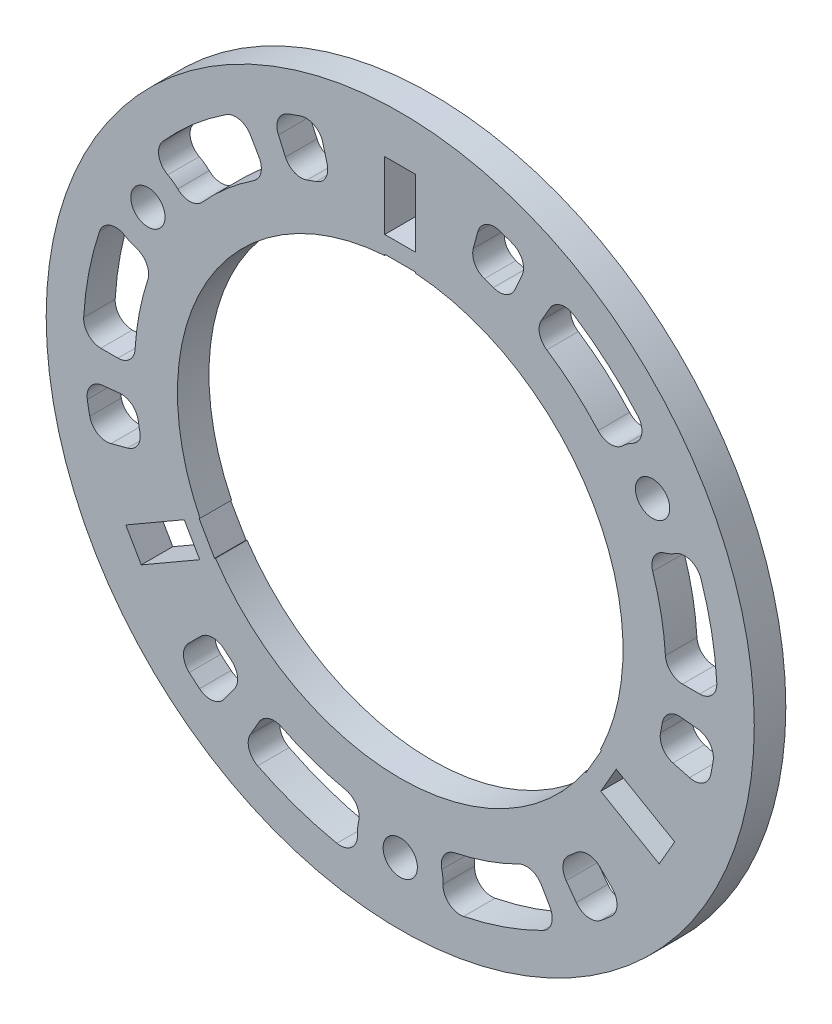
SolidWorks part; units mm, degrees
ref_plane "Front Plane" through (0, 0, 0) normal (0, 0, 1) x (1, 0, 0)
ref_plane "Top Plane" through (0, 0, 0) normal (0, 1, 0) x (1, 0, 0)
ref_plane "Right Plane" through (0, 0, 0) normal (1, 0, 0) x (0, 0, -1)
sketch "Sketch1" plane through (0, 0, 0) normal (0, 0, 1) x (1, 0, 0)
  line L0 (0, 0) -> (0, 50.8) construction
  line L1 (47.9712, -31.0114) -> (50.8422, -26.0386)
  line L2 (2.871, 57.05) -> (-2.871, 57.05)
  line L3 (2.871, 57.05) -> (2.871, 44.55)
  line L4 (2.871, 44.55) -> (-2.871, 44.55)
  line L5 (-2.871, 57.05) -> (-2.871, 44.55)
  line L6 (2.871, 57.05) -> (-2.871, 44.55) construction
  line L7 (2.871, 44.55) -> (-2.871, 57.05) construction
  line L8 (47.9712, -31.0114) -> (37.1459, -24.7614)
  line L9 (37.1459, -24.7614) -> (40.0169, -19.7886)
  line L10 (50.8422, -26.0386) -> (40.0169, -19.7886)
  line L11 (47.9712, -31.0114) -> (40.0169, -19.7886) construction
  line L12 (37.1459, -24.7614) -> (50.8422, -26.0386) construction
  line L13 (-50.8422, -26.0386) -> (-47.9712, -31.0114)
  line L14 (-50.8422, -26.0386) -> (-40.0169, -19.7886)
  line L15 (-40.0169, -19.7886) -> (-37.1459, -24.7614)
  line L16 (-47.9712, -31.0114) -> (-37.1459, -24.7614)
  line L17 (-50.8422, -26.0386) -> (-37.1459, -24.7614) construction
  line L18 (-40.0169, -19.7886) -> (-47.9712, -31.0114) construction
  line L19 (-2.871, 41.375) -> (2.871, 41.375)
  line L20 (-2.871, 41.175) -> (-2.871, 41.375)
  line L21 (2.871, 41.175) -> (2.871, 41.375)
  line L22 (34.2231, -23.0739) -> (34.3963, -23.1739)
  line L23 (37.2673, -18.2011) -> (34.3963, -23.1739)
  line L24 (37.0941, -18.1012) -> (37.2673, -18.2011)
  line L25 (-37.0941, -18.1012) -> (-37.2673, -18.2011)
  line L26 (-34.3963, -23.1739) -> (-37.2673, -18.2011)
  line L27 (0, 0) -> (32.5438, 56.3674) construction
  line L28 (-34.2231, -23.0739) -> (-34.3963, -23.1739)
  arc A0 (-2.871, 41.175) -> (-37.0941, -18.1012) centre (0, 0) ccw
  circle A1 centre (0, 0) radius 65.0875
  circle A2 centre (0, 0) radius 50.8 construction
  arc A3 (37.0941, -18.1012) -> (2.871, 41.175) centre (0, 0) ccw
  arc A4 (-34.2231, -23.0739) -> (34.2231, -23.0739) centre (0, 0) ccw
  point P21 (0, 0)
  point P32 (0, 0)
  point P34 (0, 0)
  dimension "D1" = 82.55
  dimension "D2" = 130.175
  dimension "D8" = 3.175
  dimension "D10" = 101.6
  dimension "D3" = 50.8
  dimension "D4" = 12.5
  dimension "D5" = 5.742
  dimension "D7" = 30
  dimension "D6" = 3
  dimension "D9" = 3
extrude "Boss-Extrude1" add sketch "Sketch1" along normal blind 5.842
sketch "Sketch3" plane through (0, 0, 5.842) normal (0, 0, 1) x (1, 0, 0)
  line L0 (0, 0) -> (0, 65.0875) construction
  line L1 (0, 0) -> (-56.3674, 32.5437) construction
  line L2 (-24.6063, 42.6193) -> (-29.3688, 50.8682)
  line L3 (-49.2125, 0) -> (-58.7375, 0)
  line L4 (-41.2731, 26.803) -> (-49.2614, 31.9907)
  line L5 (-43.8487, 22.342) -> (-52.3355, 26.6663)
  line L6 (43.8487, 22.342) -> (52.3355, 26.6663)
  line L7 (41.2731, 26.803) -> (49.2614, 31.9907)
  line L8 (24.6063, 42.6193) -> (29.3688, 50.8682)
  line L9 (49.2125, 0) -> (58.7375, 0)
  line L10 (-2.5756, -49.1451) -> (-3.0741, -58.657)
  line L11 (2.5756, -49.1451) -> (3.0741, -58.657)
  line L12 (24.6062, -42.6193) -> (29.3687, -50.8682)
  line L13 (-24.6063, -42.6193) -> (-29.3688, -50.8682)
  line L14 (-20.0165, 44.9579) -> (-23.8907, 53.6594)
  line L15 (-15.2024, 56.7361) -> (-12.7371, 47.5356)
  line L16 (-56.7361, -15.2024) -> (-47.5356, -12.7371)
  line L17 (-48.9429, -5.1441) -> (-58.4157, -6.1397)
  line L18 (48.9429, -5.1441) -> (58.4157, -6.1397)
  line L19 (56.7361, -15.2024) -> (47.5356, -12.7371)
  line L20 (15.2024, 56.7361) -> (12.7371, 47.5356)
  line L21 (20.0165, 44.9579) -> (23.8907, 53.6594)
  line L22 (-28.9264, -39.8137) -> (-34.525, -47.5196)
  line L23 (-41.5337, -41.5337) -> (-34.7985, -34.7985)
  line L24 (41.5337, -41.5337) -> (34.7985, -34.7985)
  line L25 (28.9264, -39.8137) -> (34.525, -47.5196)
  circle A0 centre (0, 0) radius 65.0875 construction
  arc A1 (-29.3688, 50.8682) -> (-49.2614, 31.9907) centre (0, 0) ccw
  arc A2 (-24.6063, 42.6193) -> (-41.2731, 26.803) centre (0, 0) ccw
  arc A3 (-43.8487, 22.342) -> (-49.2125, 0) centre (0, 0) ccw
  circle A4 centre (0, 0) radius 49.2125 construction
  circle A5 centre (0, 0) radius 58.7375 construction
  arc A6 (-52.3355, 26.6663) -> (-58.7375, 0) centre (0, 0) ccw
  arc A7 (58.7375, 0) -> (52.3355, 26.6663) centre (0, 0) ccw
  arc A8 (49.2614, 31.9907) -> (29.3688, 50.8682) centre (0, 0) ccw
  arc A9 (41.2731, 26.803) -> (24.6063, 42.6193) centre (0, 0) ccw
  arc A10 (49.2125, 0) -> (43.8487, 22.342) centre (0, 0) ccw
  arc A11 (-29.3688, -50.8682) -> (-3.0741, -58.657) centre (0, 0) ccw
  arc A12 (3.0741, -58.657) -> (29.3687, -50.8682) centre (0, 0) ccw
  arc A13 (2.5756, -49.1451) -> (24.6062, -42.6193) centre (0, 0) ccw
  arc A14 (-24.6063, -42.6193) -> (-2.5756, -49.1451) centre (0, 0) ccw
  arc A15 (-24.6063, 42.6193) -> (-41.2731, 26.803) centre (0, 0) ccw
  arc A16 (-29.3688, 50.8682) -> (-49.2614, 31.9907) centre (0, 0) ccw
  arc A17 (-43.8487, 22.342) -> (-49.2125, 0) centre (0, 0) ccw
  arc A18 (-52.3355, 26.6663) -> (-58.7375, 0) centre (0, 0) ccw
  arc A19 (-24.6063, -42.6193) -> (-2.5756, -49.1451) centre (0, 0) ccw
  arc A20 (-29.3688, -50.8682) -> (-3.0741, -58.657) centre (0, 0) ccw
  arc A21 (2.5756, -49.1451) -> (24.6062, -42.6193) centre (0, 0) ccw
  arc A22 (3.0741, -58.657) -> (29.3687, -50.8682) centre (0, 0) ccw
  arc A23 (58.7375, 0) -> (52.3355, 26.6663) centre (0, 0) ccw
  arc A24 (49.2125, 0) -> (43.8487, 22.342) centre (0, 0) ccw
  arc A25 (41.2731, 26.803) -> (24.6063, 42.6193) centre (0, 0) ccw
  arc A26 (49.2614, 31.9907) -> (29.3688, 50.8682) centre (0, 0) ccw
  arc A27 (-12.7371, 47.5356) -> (-20.0165, 44.9579) centre (0, 0) ccw
  arc A28 (-15.2024, 56.7361) -> (-23.8907, 53.6594) centre (0, 0) ccw
  arc A29 (-56.7361, -15.2024) -> (-58.4157, -6.1397) centre (0, 0) cw
  arc A30 (-47.5356, -12.7371) -> (-48.9429, -5.1441) centre (0, 0) cw
  arc A31 (56.7361, -15.2024) -> (58.4157, -6.1397) centre (0, 0) ccw
  arc A32 (47.5356, -12.7371) -> (48.9429, -5.1441) centre (0, 0) ccw
  arc A33 (15.2024, 56.7361) -> (23.8907, 53.6594) centre (0, 0) cw
  arc A34 (12.7371, 47.5356) -> (20.0165, 44.9579) centre (0, 0) cw
  arc A35 (-41.5337, -41.5337) -> (-34.525, -47.5196) centre (0, 0) ccw
  arc A36 (-34.7985, -34.7985) -> (-28.9264, -39.8137) centre (0, 0) ccw
  arc A37 (41.5337, -41.5337) -> (34.525, -47.5196) centre (0, 0) cw
  arc A38 (34.7985, -34.7985) -> (28.9264, -39.8137) centre (0, 0) cw
  point P8 (56.171, 17.1732)
  point P13 (49.2125, 0)
  point P38 (0, 0)
  point P63 (0, 0)
  dimension "D2" = 117.475
  dimension "D1" = 60
  dimension "D4" = 30
  dimension "D5" = 3
  dimension "D7" = 36
  dimension "D8" = 45
  dimension "D3" = 9.525
  dimension "D6" = 3
  dimension "D9" = 3
extrude "Cut-Extrude2" cut sketch "Sketch3" against normal through all contours A2 L2 A1 L4 | L5 A6 L3 A3 | L16 A30 L17 A29 | L15 A28 L14 A27 | L20 A34 L21 A33 | A9 L7 A8 L8 | A10 L9 A7 L6 | A32 L19 A31 L18 | L24 A38 L25 A37 | A13 L11 A12 L12 | A14 L13 A11 L10 | A36 L23 A35 L22 region at (-36.9066, 38.8915, 5.842) region at (-52.1343, 12.5163, 5.842) region at (52.1343, 12.5163, 5.842) region at (36.9066, 38.8915, 5.842) region at (-15.2277, -51.4078, 5.842) region at (15.2277, -51.4078, 5.842) region at (-18.0454, 50.9587, 5.842) region at (-53.1542, -9.8516, 5.842) region at (53.1542, -9.8516, 5.842) region at (18.0454, 50.9587, 5.842) region at (-35.1088, -41.1071, 5.842) region at (35.1088, -41.1071, 5.842)
fillet "Fillet1" radius 3.175 48 edges at (-52.3355, 26.6663, 2.921) (-58.4157, -6.1397, 2.921) (-43.8487, 22.342, 2.921) (-48.9429, -5.1441, 2.921) (-58.7375, 0, 2.921) (-56.7361, -15.2024, 2.921) (-47.5356, -12.7371, 2.921) (-49.2125, 0, 2.921) (-41.2731, 26.803, 2.921) (-49.2614, 31.9907, 2.921) (-20.0165, 44.9579, 2.921) (-12.7371, 47.5356, 2.921) (-15.2024, 56.7361, 2.921) (-23.8907, 53.6594, 2.921) (-29.3688, 50.8682, 2.921) (-24.6063, 42.6193, 2.921) (41.5337, -41.5337, 2.921) (34.525, -47.5196, 2.921) (34.7985, -34.7985, 2.921) (28.9264, -39.8137, 2.921) (3.0741, -58.657, 2.921) (2.5756, -49.1451, 2.921) (24.6062, -42.6193, 2.921) (29.3687, -50.8682, 2.921) (-3.0741, -58.657, 2.921) (-2.5756, -49.1451, 2.921) (-29.3688, -50.8682, 2.921) (-24.6063, -42.6193, 2.921) (-28.9264, -39.8137, 2.921) (-41.5337, -41.5337, 2.921) (-34.7985, -34.7985, 2.921) (-34.525, -47.5196, 2.921) (48.9429, -5.1441, 2.921) (58.4157, -6.1397, 2.921) (56.7361, -15.2024, 2.921) (47.5356, -12.7371, 2.921) (58.7375, 0, 2.921) (49.2125, 0, 2.921) (52.3355, 26.6663, 2.921) (43.8487, 22.342, 2.921) (49.2614, 31.9907, 2.921) (41.2731, 26.803, 2.921) (29.3688, 50.8682, 2.921) (23.8907, 53.6594, 2.921) (15.2024, 56.7361, 2.921) (24.6063, 42.6193, 2.921) (12.7371, 47.5356, 2.921) (20.0165, 44.9579, 2.921)
sketch "Sketch4" plane through (0, 0, 5.842) normal (0, 0, 1) x (1, 0, 0)
  circle A0 centre (0, 0) radius 65.0875
  circle A1 centre (0, 0) radius 65.5875
  dimension "D1" = 0.5
extrude "Boss-Extrude2" add sketch "Sketch4" against normal up to surface (5.842 mm away) up to face at (-15.0326, -50.7493, 0)
sketch "Sketch5" plane through (0, 0, 5.842) normal (0, 0, 1) x (1, 0, 0)
  line L0 (0, 0) -> (64.6093, 37.3022) construction
  line L1 (0, 0) -> (0, 44.55) construction
  line L2 (-2.871, 44.55) -> (2.871, 44.55) construction
  circle A0 centre (46.7437, 26.9875) radius 3.175
  circle A1 centre (46.7437, 26.9875) radius 7.9375
  circle A2 centre (0, -53.975) radius 7.9375
  circle A3 centre (0, -53.975) radius 3.175
  circle A4 centre (-46.7437, 26.9875) radius 7.9375
  circle A5 centre (-46.7437, 26.9875) radius 3.175
  point P17 (0, 0)
  dimension "D2" = 6.35
  dimension "D4" = 15.875
  dimension "D1" = 60
  dimension "D3" = 53.975
  dimension "D5" = 3
extrude "Boss-Extrude3" add sketch "Sketch5" against normal up to surface (5.842 mm away) up to face at (-15.0326, -50.7493, 0)
sketch "Sketch6" plane through (0, 0, 5.842) normal (0, 0, 1) x (1, 0, 0)
  circle A0 centre (46.7437, 26.9875) radius 3.175
  circle A1 centre (0, -53.975) radius 3.175
  circle A2 centre (-46.7437, 26.9875) radius 3.175
  point P9 (0, 0)
  dimension "D2" = 53.975
  dimension "D1" = 3
extrude "Cut-Extrude3" cut sketch "Sketch6" against normal through all
fillet "Fillet2" radius 3.175 12 edges at (47.2378, 34.9096, 2.921) (39.2699, 29.6606, 2.921) (45.3217, 19.1784, 2.921) (53.8515, 23.4544, 2.921) (-39.2699, 29.6606, 2.921) (-45.3217, 19.1784, 2.921) (-53.8515, 23.4544, 2.921) (-47.2378, 34.9096, 2.921) (6.0519, -48.839, 2.921) (-6.0519, -48.839, 2.921) (-6.6137, -58.364, 2.921) (6.6137, -58.364, 2.921)
